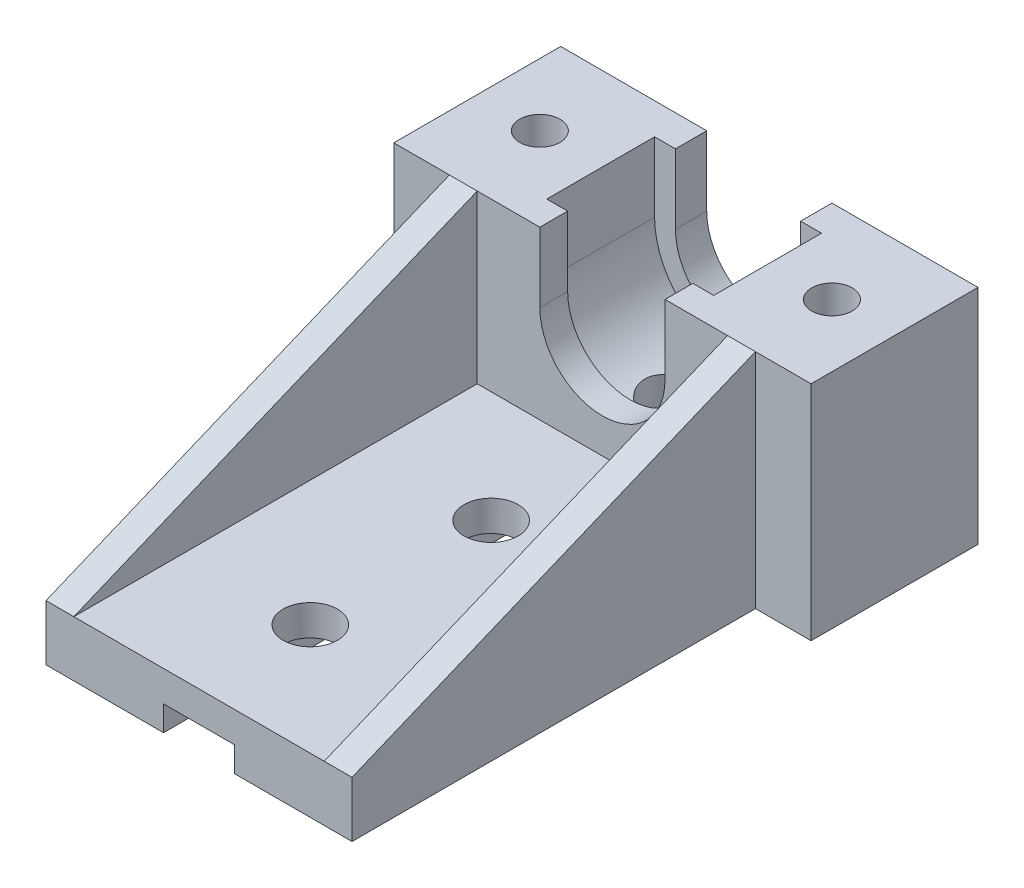
SolidWorks part; units mm, degrees
ref_plane "Front Plane" through (0, 0, 0) normal (0, 0, 1) x (1, 0, 0)
ref_plane "Top Plane" through (0, 0, 0) normal (0, 1, 0) x (1, 0, 0)
ref_plane "Right Plane" through (0, 0, 0) normal (1, 0, 0) x (0, 0, -1)
sketch "Sketch1" plane through (0, 0, 0) normal (0, 0, 1) x (1, 0, 0)
  line L0 (-5.2806, 25) -> (-5.2806, 41)
  line L2 (-5.2806, 41) -> (5.2194, 41)
  line L3 (24.7194, 41) -> (24.7194, 25)
  line L5 (24.7194, 25) -> (12.2694, 25)
  line L6 (12.2694, 25) -> (12.2694, 26.8)
  line L7 (12.2694, 26.8) -> (7.1694, 26.8)
  line L8 (7.1694, 26.8) -> (7.1694, 25)
  line L9 (7.1694, 25) -> (-5.2806, 25)
  line L10 (9.7194, 26.8) -> (9.7194, 45.2) construction
  line L11 (14.2194, 41) -> (24.7194, 41)
  line L13 (5.2194, 36) -> (5.2194, 41)
  line L15 (14.2194, 36) -> (14.2194, 41)
  arc A0 (5.2194, 36) -> (14.2194, 36) centre (9.7194, 36) ccw
  dimension "D3" = 4.5
  dimension "D1" = 5.1
  dimension "D2" = 1.8
  dimension "D4" = 16
  dimension "D5" = 30
  dimension "D6" = 5
extrude "Boss-Extrude1" add sketch "Sketch1" against normal blind 12 contours L13 L2 L0 L9 L8 L7 L6 L5 L3 L11 L15 A0
sketch "Sketch2" plane through (0, 0, 0) normal (0, 0, 1) x (1, 0, 0)
  line L0 (14.2194, 41) -> (24.7194, 41) construction
  line L2 (3.7194, 36) -> (3.7194, 41)
  line L3 (3.7194, 41) -> (15.7194, 41)
  line L4 (15.7194, 36) -> (15.7194, 41)
  arc A0 (3.7194, 36) -> (15.7194, 36) centre (9.7194, 36) ccw
  dimension "D1" = 12
extrude "Cut-Extrude1" cut sketch "Sketch2" against normal blind 7.75 from offset 2 offset against normal yes
sketch "Sketch3" plane through (0, 41, 0) normal (0, 1, 0) x (1, 0, 0)
  line L0 (24.7194, 6) -> (-5.2806, 6) construction
  line L1 (24.7194, 12) -> (24.7194, 0) construction
  line L2 (-5.2806, 12) -> (-5.2806, 0) construction
  line L3 (5.2194, 12) -> (14.2194, 12) construction
  line L4 (9.7194, 12) -> (9.7194, 0) construction
  circle A0 centre (20.2194, 6) radius 1.45
  circle A1 centre (-0.7806, 6) radius 1.45
  dimension "D2" = 2.9
  dimension "D1" = 4.5
extrude "Cut-Extrude2" cut sketch "Sketch3" against normal blind 18
sketch "Sketch4" plane through (0, 0, 0) normal (0, 0, 1) x (1, 0, 0)
  line L0 (-1.2806, 25) -> (-1.2806, 29)
  line L1 (7.1694, 25) -> (-5.2806, 25) construction
  line L2 (-1.2806, 29) -> (20.7194, 29)
  line L5 (12.2694, 26.8) -> (7.1694, 26.8)
  line L6 (7.1694, 26.8) -> (7.1694, 25)
  line L7 (7.1694, 25) -> (-1.2806, 25)
  line L8 (12.2694, 25) -> (20.7194, 25)
  line L9 (12.2694, 26.8) -> (12.2694, 25)
  line L10 (20.7194, 25) -> (20.7194, 29)
  dimension "D2" = 4
extrude "Boss-Extrude2" add sketch "Sketch4" along normal blind 29
sketch "Sketch5" plane through (0, 29, 0) normal (0, 1, 0) x (1, 0, 0)
  line L0 (9.7194, -29) -> (9.7194, 0) construction
  line L1 (20.7194, -29) -> (-1.2806, -29) construction
  line L2 (20.7194, 0) -> (-1.2806, 0) construction
  circle A0 centre (9.7194, -21) radius 1.95
  circle A1 centre (9.7194, -8) radius 1.95
  circle A3 centre (9.7194, 5) radius 1.95
  dimension "D1" = 3.9
  dimension "D2" = 13
  dimension "D3" = 8
  dimension "D4" = 13
extrude "Cut-Extrude3" cut sketch "Sketch5" against normal mid plane 29
sketch "Sketch6" plane through (-1.2806, 0, 0) normal (-1, 0, 0) x (0, 0, 1)
  line L0 (29, 29) -> (0, 41)
  line L1 (0, 41) -> (0, 29)
  line L2 (0, 29) -> (29, 29)
extrude "Boss-Extrude3" add sketch "Sketch6" against normal blind 2
extrude "Boss-Extrude4" add sketch "Sketch6<2>" along normal blind 2 from offset 22 offset against normal yes
sketch "Sketch6<2>" plane through (-1.2806, 0, 0) normal (-1, 0, 0) x (0, 0, 1) same geometry as "Sketch6"
